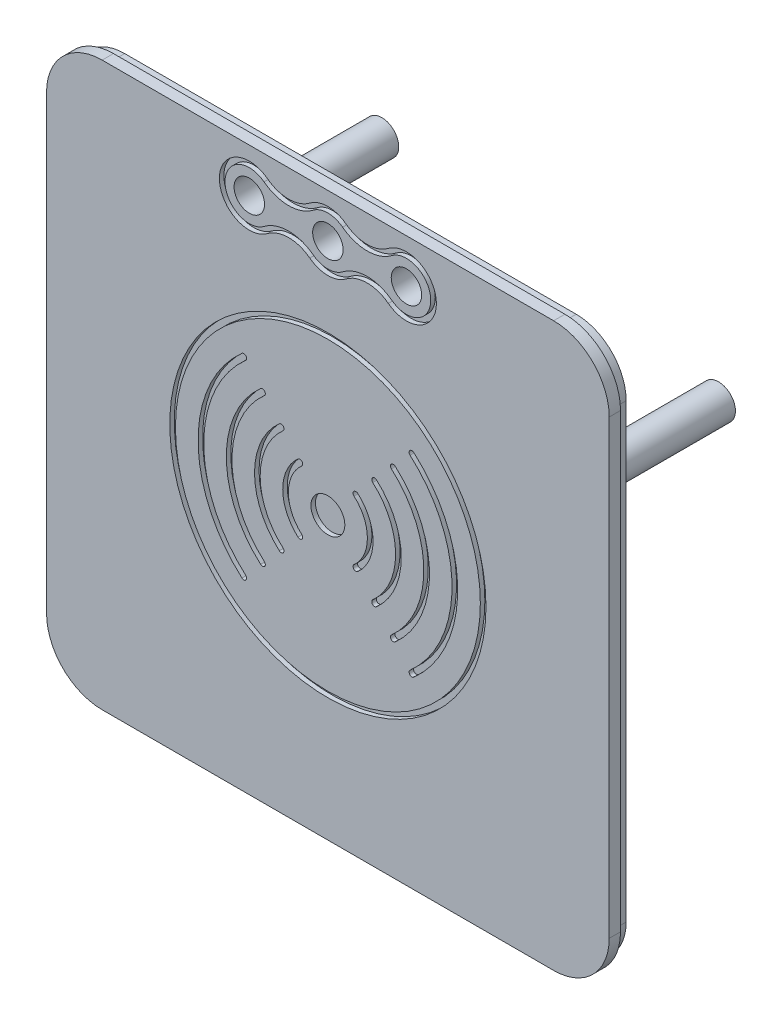
SolidWorks part; units mm, degrees
ref_plane "Alzado" through (0, 0, 0) normal (0, 0, 1) x (1, 0, 0)
ref_plane "Planta" through (0, 0, 0) normal (0, 1, 0) x (1, 0, 0)
ref_plane "Vista lateral" through (0, 0, 0) normal (1, 0, 0) x (0, 0, -1)
sketch "Croquis1" plane through (0, 0, 0) normal (0, 0, 1) x (1, 0, 0)
  line L4 (-24.067, 40) -> (-24.067, -40)
  line L5 (-14.217, -49.85) -> (65.783, -49.85)
  line L6 (75.633, -40) -> (75.633, 40)
  line L7 (65.783, 49.85) -> (-14.217, 49.85)
  line L8 (-24.367, 40) -> (-24.367, -40)
  line L9 (-14.217, -50.15) -> (65.783, -50.15)
  line L10 (75.933, -40) -> (75.933, 40)
  line L11 (65.783, 50.15) -> (-14.217, 50.15)
  arc A4 (-24.067, -40) -> (-14.217, -49.85) centre (-14.217, -40) ccw
  arc A5 (65.783, -49.85) -> (75.633, -40) centre (65.783, -40) ccw
  arc A6 (75.633, 40) -> (65.783, 49.85) centre (65.783, 40) ccw
  arc A7 (-14.217, 49.85) -> (-24.067, 40) centre (-14.217, 40) ccw
  arc A8 (-24.367, -40) -> (-14.217, -50.15) centre (-14.217, -40) ccw
  arc A9 (65.783, -50.15) -> (75.933, -40) centre (65.783, -40) ccw
  arc A10 (75.933, 40) -> (65.783, 50.15) centre (65.783, 40) ccw
  arc A11 (-14.217, 50.15) -> (-24.367, 40) centre (-14.217, 40) ccw
  dimension "D1" = 0.3
extrude "Saliente-Extruir1" add sketch "Croquis1" along normal blind 2 contours L4 A4 L5 A5 L6 A6 L7 A7
sketch "Croquis2" plane through (0, 0, 0) normal (0, 0, -1) x (-1, 0, 0)
  line L4 (14.217, 49.85) -> (-65.783, 49.85)
  line L5 (-75.633, 40) -> (-75.633, -40)
  line L6 (-65.783, -49.85) -> (14.217, -49.85)
  line L7 (24.067, -40) -> (24.067, 40)
  line L8 (14.217, 49.85) -> (-65.783, 49.85)
  line L9 (-75.633, 40) -> (-75.633, -40)
  line L10 (-65.783, -49.85) -> (14.217, -49.85)
  line L11 (24.067, -40) -> (24.067, 40)
  line L16 (14.217, 48.85) -> (-65.783, 48.85)
  line L17 (-74.633, 40) -> (-74.633, -40)
  line L18 (-65.783, -48.85) -> (14.217, -48.85)
  line L19 (23.067, -40) -> (23.067, 40)
  line L20 (14.217, 48.85) -> (-65.783, 48.85)
  line L21 (-74.633, 40) -> (-74.633, -40)
  line L22 (-65.783, -48.85) -> (14.217, -48.85)
  line L23 (23.067, -40) -> (23.067, 40)
  arc A4 (24.067, 40) -> (14.217, 49.85) centre (14.217, 40) ccw
  arc A5 (-65.783, 49.85) -> (-75.633, 40) centre (-65.783, 40) ccw
  arc A6 (-75.633, -40) -> (-65.783, -49.85) centre (-65.783, -40) ccw
  arc A7 (14.217, -49.85) -> (24.067, -40) centre (14.217, -40) ccw
  arc A8 (24.067, 40) -> (14.217, 49.85) centre (14.217, 40) ccw
  arc A9 (-65.783, 49.85) -> (-75.633, 40) centre (-65.783, 40) ccw
  arc A10 (-75.633, -40) -> (-65.783, -49.85) centre (-65.783, -40) ccw
  arc A11 (14.217, -49.85) -> (24.067, -40) centre (14.217, -40) ccw
  arc A16 (23.067, 40) -> (14.217, 48.85) centre (14.217, 40) ccw
  arc A17 (-65.783, 48.85) -> (-74.633, 40) centre (-65.783, 40) ccw
  arc A18 (-74.633, -40) -> (-65.783, -48.85) centre (-65.783, -40) ccw
  arc A19 (14.217, -48.85) -> (23.067, -40) centre (14.217, -40) ccw
  arc A20 (23.067, 40) -> (14.217, 48.85) centre (14.217, 40) ccw
  arc A21 (-65.783, 48.85) -> (-74.633, 40) centre (-65.783, 40) ccw
  arc A22 (-74.633, -40) -> (-65.783, -48.85) centre (-65.783, -40) ccw
  arc A23 (14.217, -48.85) -> (23.067, -40) centre (14.217, -40) ccw
  dimension "D1" = 0
  dimension "D2" = 1
extrude "Saliente-Extruir2" add sketch "Croquis2" along normal blind 2 contours A20 L20 A21 L21 A22 L22 A23 L23
sketch "Croquis3" plane through (0, 0, -2) normal (0, 0, -1) x (-1, 0, 0)
  line L0 (-25.783, 48.85) -> (-25.783, 20.3)
  line L1 (14.217, 48.85) -> (-65.783, 48.85) construction
  line L3 (-45.783, 0) -> (-45.783, 20.3)
  line L4 (-45.783, 20.3) -> (-5.783, 20.3)
  line L5 (-45.783, 0) -> (-45.783, -40)
  line L6 (-45.783, -40) -> (-5.783, -40)
  line L7 (-5.783, 0) -> (-5.783, -40)
  line L8 (-5.783, 0) -> (-5.783, 20.3)
  point P10 (-25.783, -40)
  point P12 (-25.783, 20.3)
  dimension "D1" = 60.3
  dimension "D2" = 40
extrude "Cortar-Extruir1" cut sketch "Croquis3" against normal blind 2 contours L7 L8 L4 L3 L5 L6 region at (25.783, -9.85, -2)
sketch "Croquis5" plane through (0, 0, 2) normal (0, 0, 1) x (1, 0, 0)
  line L0 (25.783, 55.864) -> (25.783, -43.836) construction
  line L1 (25.783, 0) -> (-24.067, 0) construction
  line L2 (25.783, 49.85) -> (25.783, 41.4015)
  line L3 (65.783, 49.85) -> (-14.217, 49.85) construction
  line L4 (75.633, 0) -> (69.7393, 0)
  line L5 (75.633, -40) -> (75.633, 40) construction
  circle A0 centre (25.783, 0) radius 3
  arc A1 (21.15, 5.2473) -> (21.15, -5.2473) centre (25.783, 0) ccw
  arc A2 (20.4881, 5.997) -> (20.4881, -5.997) centre (25.783, 0) ccw
  arc A3 (17.8406, 8.9955) -> (17.8406, -8.9955) centre (25.783, 0) ccw
  arc A4 (17.1788, 9.7451) -> (17.1788, -9.7451) centre (25.783, 0) ccw
  arc A5 (14.5313, 12.7436) -> (14.5313, -12.7436) centre (25.783, 0) ccw
  arc A6 (13.8694, 13.4932) -> (13.8694, -13.4932) centre (25.783, 0) ccw
  arc A7 (11.222, 16.4917) -> (11.222, -16.4917) centre (25.783, 0) ccw
  arc A8 (10.5601, 17.2413) -> (10.5601, -17.2413) centre (25.783, 0) ccw
  arc A9 (41.006, -17.2413) -> (41.006, 17.2413) centre (25.783, 0) ccw
  arc A10 (40.3441, -16.4917) -> (40.3441, 16.4917) centre (25.783, 0) ccw
  arc A11 (37.6966, -13.4932) -> (37.6966, 13.4932) centre (25.783, 0) ccw
  arc A12 (37.0348, -12.7436) -> (37.0348, 12.7436) centre (25.783, 0) ccw
  arc A13 (34.3873, -9.7451) -> (34.3873, 9.7451) centre (25.783, 0) ccw
  arc A14 (33.7254, -8.9955) -> (33.7254, 8.9955) centre (25.783, 0) ccw
  arc A15 (31.078, -5.997) -> (31.078, 5.997) centre (25.783, 0) ccw
  arc A16 (30.4161, -5.2473) -> (30.4161, 5.2473) centre (25.783, 0) ccw
  arc A17 (11.222, 16.4917) -> (10.5601, 17.2413) centre (10.891, 16.8665) ccw
  arc A18 (14.5313, 12.7436) -> (13.8694, 13.4932) centre (14.2004, 13.1184) ccw
  arc A19 (17.8406, 8.9955) -> (17.1788, 9.7451) centre (17.5097, 9.3703) ccw
  arc A20 (21.15, 5.2473) -> (20.4881, 5.997) centre (20.819, 5.6222) ccw
  arc A21 (20.4881, -5.997) -> (21.15, -5.2473) centre (20.819, -5.6222) ccw
  arc A22 (10.5601, -17.2413) -> (11.222, -16.4917) centre (10.891, -16.8665) ccw
  arc A23 (13.8694, -13.4932) -> (14.5313, -12.7436) centre (14.2004, -13.1184) ccw
  arc A24 (17.1788, -9.7451) -> (17.8406, -8.9955) centre (17.5097, -9.3703) ccw
  arc A25 (41.006, 17.2413) -> (40.3441, 16.4917) centre (40.675, 16.8665) ccw
  arc A26 (37.6966, 13.4932) -> (37.0348, 12.7436) centre (37.3657, 13.1184) ccw
  arc A27 (34.3873, 9.7451) -> (33.7254, 8.9955) centre (34.0564, 9.3703) ccw
  arc A28 (31.078, 5.997) -> (30.4161, 5.2473) centre (30.747, 5.6222) ccw
  arc A29 (30.4161, -5.2473) -> (31.078, -5.997) centre (30.747, -5.6222) ccw
  arc A30 (33.7254, -8.9955) -> (34.3873, -9.7451) centre (34.0564, -9.3703) ccw
  arc A31 (37.0348, -12.7436) -> (37.6966, -13.4932) centre (37.3657, -13.1184) ccw
  arc A32 (40.3441, -16.4917) -> (41.006, -17.2413) centre (40.675, -16.8665) ccw
  circle A33 centre (25.783, 0) radius 27.0152
  circle A34 centre (25.783, 0) radius 28.0152
  point P63 (0, 0)
  point P64 (0, 0)
  point P65 (-5.3286, 6.014)
  point P66 (0, 0)
  point P67 (0, 0)
  dimension "D1" = 6
  dimension "D2" = 14
  dimension "D3" = 16
  dimension "D5" = 25
  dimension "D6" = 30
  dimension "D7" = 35
  dimension "D8" = 40
  dimension "D9" = 45
  dimension "D10" = 55.0304
extrude "Cortar-Extruir2" cut sketch "Croquis5" against normal blind 0.8 contours A0 | A34 A33 | A10 A32 A9 A25 | A12 A31 A11 A26 | A14 A30 A13 A27 | A16 A29 A15 A28 | A2 A21 A1 A20 | A4 A24 A3 A19 | A6 A23 A5 A18 | A8 A22 A7 A17 region at (25.783, 0, 2) region at (18.6556, 0, 2) region at (13.5788, 0, 2) region at (8.502, 0, 2) region at (3.4252, 0, 2) region at (40.5685, -16.9606, 2) region at (37.2015, -13.2633, 2) region at (33.8346, -9.566, 2) region at (30.4678, -5.8687, 2) region at (-1.4398, 0, 2)
sketch "Croquis6" plane through (0, 0, 2) normal (0, 0, 1) x (1, 0, 0)
  line L0 (25.783, 28.0152) -> (25.783, 49.85) construction
  line L1 (65.783, 49.85) -> (-14.217, 49.85) construction
  line L2 (25.783, 42.0844) -> (39.7066, 42.0844) construction
  line L3 (32.7448, 42.0844) -> (32.7448, 47.8931) construction
  circle A0 centre (25.783, 0) radius 28.0152 construction
  circle A1 centre (25.783, 42.0844) radius 2.7
  circle A2 centre (39.7066, 42.0844) radius 2.7
  circle A3 centre (11.8594, 42.0844) radius 2.7
extrude "Cortar-Extruir3" cut sketch "Croquis6" against normal blind 11.8
sketch "Croquis7" plane through (0, 0, -2) normal (0, 0, -1) x (-1, 0, 0)
  circle A0 centre (2.6202, -5.3233) radius 3
  circle A1 centre (-59.659, 16.7543) radius 3
  circle A2 centre (0, 27.4667) radius 3
extrude "Saliente-Extruir3" add sketch "Croquis7" along normal up to surface (31.34 mm away)
sketch "Croquis8" plane through (0, 0, -33.34) normal (0, 0, -1) x (-1, 0, 0)
  circle A0 centre (2.6202, -5.3233) radius 2
  circle A1 centre (0, 27.4667) radius 2
  circle A2 centre (-59.659, 16.7543) radius 2
extrude "Cortar-Extruir4" cut sketch "Croquis8" against normal blind 5 contours A0 | A1 | A2 region at (-2.6202, -5.3233, -33.34) region at (0, 27.4667, -33.34) region at (59.659, 16.7543, -33.34)
sketch "Croquis9" plane through (0, 0, 0) normal (0, 0, -1) x (-1, 0, 0)
  line L1 (-15.4663, -39.1768) -> (-36.0362, -39.1768)
  line L2 (-15.4663, -39.1768) -> (-15.4663, -36.3089)
  line L3 (-15.4663, -36.3089) -> (-36.0362, -36.3089)
  line L4 (-36.0362, -39.1768) -> (-36.0362, -36.3089)
extrude "Cortar-Extruir5" cut sketch "Croquis9" against normal blind 1
sketch "Croquis10" plane through (0, 0, -2) normal (0, 0, -1) x (-1, 0, 0)
  line L0 (-5.783, 20.3) -> (-5.783, -40) construction
  line L1 (-5.783, -8.33) -> (-5.0975, -8.33)
  line L2 (-5.783, -8.33) -> (-5.783, 0)
  line L3 (-5.783, 0) -> (-5.0975, 0)
  line L4 (-5.0975, -8.33) -> (-5.0975, 0)
  line L5 (-45.783, -40) -> (-45.783, 20.3) construction
  line L6 (-45.783, 0) -> (-46.4844, 0)
  line L7 (-45.783, 0) -> (-45.783, -8.33)
  line L8 (-45.783, -8.33) -> (-46.4844, -8.33)
  line L9 (-46.4844, 0) -> (-46.4844, -8.33)
extrude "Saliente-Extruir4" add sketch "Croquis10" along normal blind 1
sketch "Croquis11" plane through (5.783, 0, 0) normal (1, 0, 0) x (0, 0, -1)
  line L0 (3, 0) -> (3, -8.33) construction
  line L1 (3, -8.33) -> (1.9996, -8.33)
  line L2 (3, -8.33) -> (3, 0)
  line L3 (3, 0) -> (1.9996, 0)
  line L4 (1.9996, -8.33) -> (1.9996, 0)
  line L5 (3, -8.33) -> (2, -8.33) construction
  line L6 (3, 0) -> (2, 0) construction
extrude "Saliente-Extruir5" add sketch "Croquis11" along normal blind 0.3
sketch "Croquis12" plane through (45.783, 0, 0) normal (-1, 0, 0) x (0, 0, 1)
  line L0 (-3, 0) -> (-2, 0) construction
  line L1 (-3, 0) -> (-1.9931, 0)
  line L2 (-3, 0) -> (-3, -8.3233)
  line L3 (-3, -8.3233) -> (-1.9931, -8.3233)
  line L4 (-1.9931, 0) -> (-1.9931, -8.3233)
  line L5 (-33.34, -8.3233) -> (-2, -8.3233) construction
extrude "Saliente-Extruir6" add sketch "Croquis12" along normal blind 0.5
chamfer "Chaflán1" distance 0.3 angle 46 2 edges at (45.283, -4.1616, -1.9931) (6.083, -4.165, -1.9996) first distance on face at (45.533, -4.1616, -1.9931) first distance on face at (5.933, -4.165, -1.9996)
sketch "Croquis13" plane through (0, 0, 2) normal (0, 0, 1) x (1, 0, 0)
  line L0 (18.8212, 42.0844) -> (18.8212, 44.0844) construction
  line L1 (39.7066, 42.0844) -> (25.783, 42.0844) construction
  line L2 (25.783, 42.0844) -> (11.8594, 42.0844) construction
  line L3 (32.7448, 40.1334) -> (32.7448, 40.0844) construction
  line L4 (25.783, 46.3866) -> (25.783, 37.7821) construction
  arc A0 (14.468, 45.5056) -> (14.468, 38.6631) centre (11.8594, 42.0844) ccw
  arc A1 (23.1745, 38.6631) -> (28.3916, 38.6631) centre (25.783, 42.0844) ccw
  arc A2 (37.0981, 38.6631) -> (37.0981, 45.5056) centre (39.7066, 42.0844) ccw
  arc A3 (14.468, 38.6631) -> (23.1745, 38.6631) centre (18.8212, 32.9538) cw
  arc A4 (14.468, 45.5056) -> (23.1745, 45.5056) centre (18.8212, 51.2149) ccw
  arc A5 (37.0981, 45.5056) -> (28.3916, 45.5056) centre (32.7448, 51.2149) cw
  arc A6 (37.0981, 38.6631) -> (28.3916, 38.6631) centre (32.7448, 32.9538) ccw
  arc A7 (28.3916, 45.5056) -> (23.1745, 45.5056) centre (25.783, 42.0844) ccw
  arc A8 (15.0743, 37.8679) -> (22.5681, 37.8679) centre (18.8212, 32.9538) cw
  arc A9 (22.5681, 37.8679) -> (28.9979, 37.8679) centre (25.783, 42.0844) ccw
  arc A10 (36.4917, 37.8679) -> (28.9979, 37.8679) centre (32.7448, 32.9538) ccw
  arc A11 (36.4917, 37.8679) -> (36.4917, 46.3008) centre (39.7066, 42.0844) ccw
  arc A12 (36.4917, 46.3008) -> (28.9979, 46.3008) centre (32.7448, 51.2149) cw
  arc A13 (28.9979, 46.3008) -> (22.5681, 46.3008) centre (25.783, 42.0844) ccw
  arc A14 (15.0743, 46.3008) -> (22.5681, 46.3008) centre (18.8212, 51.2149) ccw
  arc A15 (15.0743, 46.3008) -> (15.0743, 37.8679) centre (11.8594, 42.0844) ccw
  dimension "D1" = 1
extrude "Cortar-Extruir6" cut sketch "Croquis13" against normal blind 0.8
